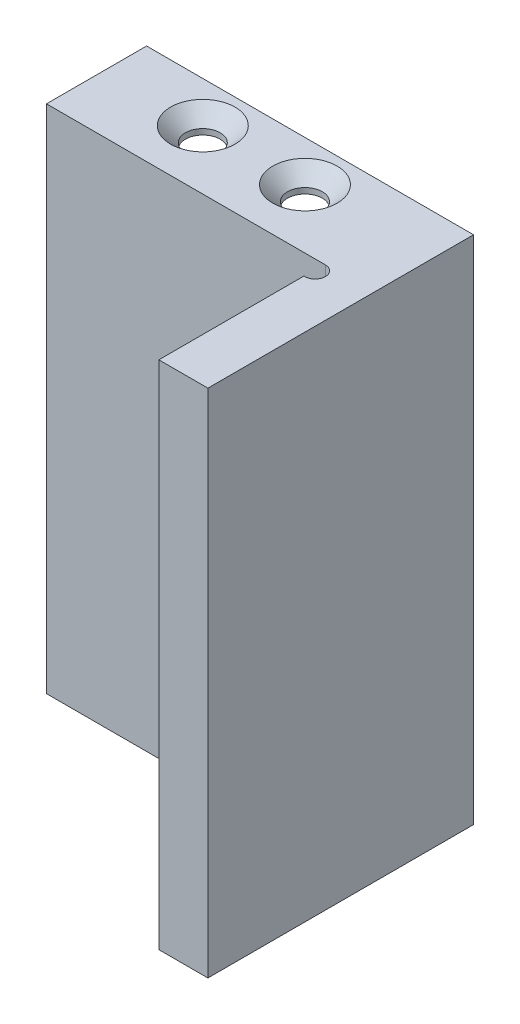
SolidWorks part; units mm, degrees
ref_plane "Front Plane" through (0, 0, 0) normal (0, 0, 1) x (1, 0, 0)
ref_plane "Top Plane" through (0, 0, 0) normal (0, 1, 0) x (1, 0, 0)
ref_plane "Right Plane" through (0, 0, 0) normal (1, 0, 0) x (0, 0, -1)
sketch "Skizze1" plane through (0, 0, 0) normal (0, 1, 0) x (1, 0, 0)
  line L1 (-16, 13) -> (16, 13)
  line L2 (-16, 13) -> (-16, -13)
  line L3 (-16, -13) -> (16, -13)
  line L4 (16, 13) -> (16, -13)
  line L5 (0, -13) -> (0, 13) construction
  line L6 (-16, 0) -> (16, 0) construction
  point P96 (0, 0)
  dimension "D1" = 32
  dimension "D2" = 26
extrude "Aufsatz-Linear austragen1" add sketch "Skizze1" along normal blind 2
hole_wizard "Formsenkung für M3 Linsensenkschraube mit Schlitz1" positions "Skizze7" profile "Skizze8" countersink size "M3" standard "DIN"
sketch "Skizze7" plane through (0, 2, 0) normal (0, 1, 0) x (1, 0, 0)
  line L0 (16, 9) -> (-16, 9) construction
  line L1 (16, -13) -> (16, 13) construction
  line L2 (-16, 13) -> (-16, -13) construction
  line L4 (16, 13) -> (-16, 13) construction
  line L5 (-1.5, 13) -> (-1.5, -13) construction
  point P0 (-6.5, 9)
  point P2 (3.5, 9)
  dimension "D1" = 4
  dimension "D2" = 10
  dimension "D3" = 17.5
sketch "Skizze8" plane through (-6.5, 2, -9) normal (1, 0, 0) x (0, 0, 1)
  line L0 (0, 0) -> (0, 9.5215)
  line L1 (0, 9.5215) -> (1.7, 8.5)
  line L2 (1.7, 8.5) -> (1.7, 1.45)
  line L3 (1.7, 1.45) -> (3.15, 0)
  line L5 (3.15, 0) -> (0, 0)
  line L6 (-1.7, 1.45) -> (-3.15, 0) construction
  line L10 (0, 9.5215) -> (-1.7, 8.5) construction
  line L11 (0, -6.35) -> (0, 107.95) construction
  dimension "Bohrerdurchmesser" = 3.4
  dimension "Bohrungstiefe" = 8.5
  dimension "Senkdurchmesser (Oben)" = 6.3
  dimension "Senkwinkel (Oben)" = 90
  dimension "Spitzenwinkel" = 118
sketch "Skizze11" plane through (0, 0, 0) normal (0, -1, 0) x (1, 0, 0)
  line L0 (16, 13) -> (16, -13)
  line L1 (14, -5) -> (-16, -5)
  line L2 (11.2, -3.2) -> (11.2, 13)
  line L3 (11.2, -3.2) -> (-16, -3.2)
  line L4 (-16, -5) -> (-16, -3.2)
  line L5 (-16, 13) -> (16, 13) construction
  line L6 (11.2, 13) -> (16, 13)
  line L10 (14, -5) -> (14, -13)
  line L11 (16, -13) -> (-16, -13) construction
  line L12 (14, -13) -> (16, -13)
  line L13 (-16, -13) -> (-16, 13) construction
  dimension "D1" = 4.8
  dimension "D2" = 2
  dimension "D3" = 1.8
  dimension "D4" = 9.8
extrude "Aufsatz-Linear austragen2" add sketch "Skizze11" along normal blind 48
sketch "Skizze12" plane through (0, 2, 0) normal (0, 1, 0) x (1, 0, 0)
  line L0 (11.2, 3.2) -> (11.2, -13)
  line L2 (-16, -13) -> (16, -13) construction
  line L3 (16, -13) -> (16, 13) construction
  line L5 (11.2, 3.2) -> (-16, 3.2)
  line L7 (-16, 3.2) -> (-16, -13)
  line L8 (-16, -13) -> (11.2, -13)
  line L10 (-16, 13) -> (-16, -13) construction
  dimension "D1" = 16.2
  dimension "D2" = 4.8
extrude "Schnitt-Linear austragen3" cut sketch "Skizze12" against normal through all
hole_wizard "Ø3.2 (3.2) Durchmesser Bohrung1" positions "Skizze13" profile "Skizze14" hole size "Ø3.2" standard "DIN" end condition up to next
sketch "Skizze13" plane through (0, 0, -3.2) normal (0, 0, 1) x (1, 0, 0)
  line L0 (11.2, 2) -> (-16, 2) construction
  line L1 (16, 2) -> (16, -48) construction
  point P0 (-1, -42.5)
  dimension "D1" = 44.5
  dimension "D2" = 17
sketch "Skizze14" plane through (-1, -42.5, -3.2) normal (1, 0, 0) x (0, -1, 0)
  line L0 (0, 0) -> (0, 1.8)
  line L1 (0, 1.8) -> (1.6, 1.8)
  line L2 (1.6, 1.8) -> (1.6, 0)
  line L5 (1.6, 0) -> (0, 0)
  line L11 (0, -6.35) -> (0, 107.95) construction
  dimension "Bohrerdurchmesser" = 3.2
  dimension "Bohrungstiefe" = 1.8
sketch "Skizze16" plane through (0, 2, 0) normal (0, 1, 0) x (1, 0, 0)
  line L1 (11.2, 3.2) -> (12.3, 3.2)
  line L2 (11.2, 3.2) -> (11.2, 1.2)
  line L3 (11.2, 1.2) -> (12.3, 1.2)
  line L4 (12.3, 3.2) -> (12.3, 1.2)
  line L5 (11.75, 1.2) -> (11.75, 3.2) construction
  line L6 (11.2, 2.2) -> (12.3, 2.2) construction
  point P88 (11.75, 2.2)
  dimension "D1" = 1.1
  dimension "D2" = 2
extrude "Schnitt-Linear austragen5" cut sketch "Skizze16" against normal through all
fillet "Verrundung1" radius 1 2 edges at (12.3, -23, -3.2) (12.3, -23, -1.2)
